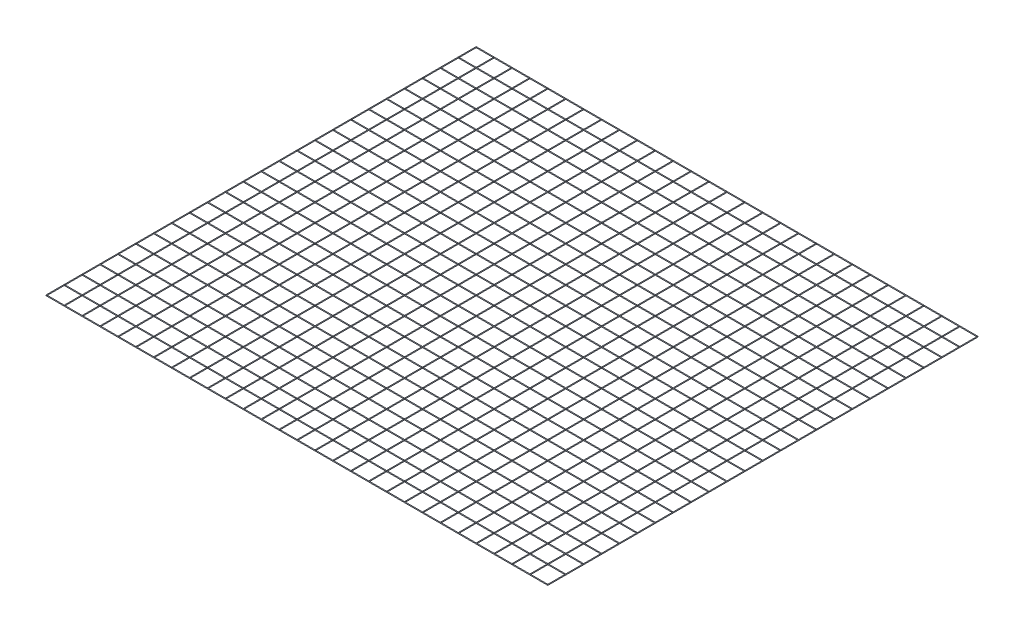
SolidWorks part; units mm, degrees
ref_plane "Piano frontale" through (0, 0, 0) normal (0, 0, 1) x (1, 0, 0)
ref_plane "Piano superiore" through (0, 0, 0) normal (0, 1, 0) x (1, 0, 0)
ref_plane "Piano destro" through (0, 0, 0) normal (1, 0, 0) x (0, 0, -1)
sketch "Schizzo1" plane through (0, 0, 0) normal (0, 0, 1) x (1, 0, 0)
  circle A0 centre (0, 0) radius 1
  circle A1 centre (50, 0) radius 1
  circle A2 centre (100, 0) radius 1
  circle A3 centre (150, 0) radius 1
  circle A4 centre (200, 0) radius 1
  circle A5 centre (250, 0) radius 1
  circle A6 centre (300, 0) radius 1
  circle A7 centre (350, 0) radius 1
  circle A8 centre (400, 0) radius 1
  circle A9 centre (450, 0) radius 1
  circle A10 centre (500, 0) radius 1
  circle A11 centre (550, 0) radius 1
  circle A12 centre (600, 0) radius 1
  circle A13 centre (650, 0) radius 1
  circle A14 centre (700, 0) radius 1
  circle A15 centre (750, 0) radius 1
  circle A16 centre (800, 0) radius 1
  circle A17 centre (850, 0) radius 1
  circle A18 centre (900, 0) radius 1
  circle A19 centre (950, 0) radius 1
  circle A20 centre (1000, 0) radius 1
  circle A21 centre (1050, 0) radius 1
  circle A22 centre (1100, 0) radius 1
  circle A23 centre (1150, 0) radius 1
  circle A24 centre (1200, 0) radius 1
  circle A25 centre (1250, 0) radius 1
  circle A26 centre (1300, 0) radius 1
  circle A27 centre (1350, 0) radius 1
  circle A28 centre (1400, 0) radius 1
  circle A33 centre (1450, 0) radius 1 [skipped]
  circle A34 centre (1500, 0) radius 1 [skipped]
  circle A35 centre (1550, 0) radius 1 [skipped]
  circle A36 centre (1600, 0) radius 1 [skipped]
  dimension "D1" = 2
  dimension "D2" = 33
extrude "Estrusione-Estrusione1" add sketch "Schizzo1" along normal blind 1200
sketch "Schizzo2" plane through (0, 0, 0) normal (1, 0, 0) x (0, 0, -1)
  circle A0 centre (0, 0) radius 1
  circle A1 centre (-50, 0) radius 1
  circle A2 centre (-100, 0) radius 1
  circle A3 centre (-150, 0) radius 1
  circle A4 centre (-200, 0) radius 1
  circle A5 centre (-250, 0) radius 1
  circle A6 centre (-300, 0) radius 1
  circle A7 centre (-350, 0) radius 1
  circle A8 centre (-400, 0) radius 1
  circle A9 centre (-450, 0) radius 1
  circle A10 centre (-500, 0) radius 1
  circle A11 centre (-550, 0) radius 1
  circle A12 centre (-600, 0) radius 1
  circle A13 centre (-650, 0) radius 1
  circle A14 centre (-700, 0) radius 1
  circle A15 centre (-750, 0) radius 1
  circle A16 centre (-800, 0) radius 1
  circle A17 centre (-850, 0) radius 1
  circle A18 centre (-900, 0) radius 1
  circle A19 centre (-950, 0) radius 1
  circle A20 centre (-1000, 0) radius 1
  circle A21 centre (-1050, 0) radius 1
  circle A22 centre (-1100, 0) radius 1
  circle A23 centre (-1150, 0) radius 1
  circle A24 centre (-1200, 0) radius 1
  dimension "D1" = 2
  dimension "D2" = 25
extrude "Estrusione-Estrusione2" add sketch "Schizzo2" along normal blind 1400
